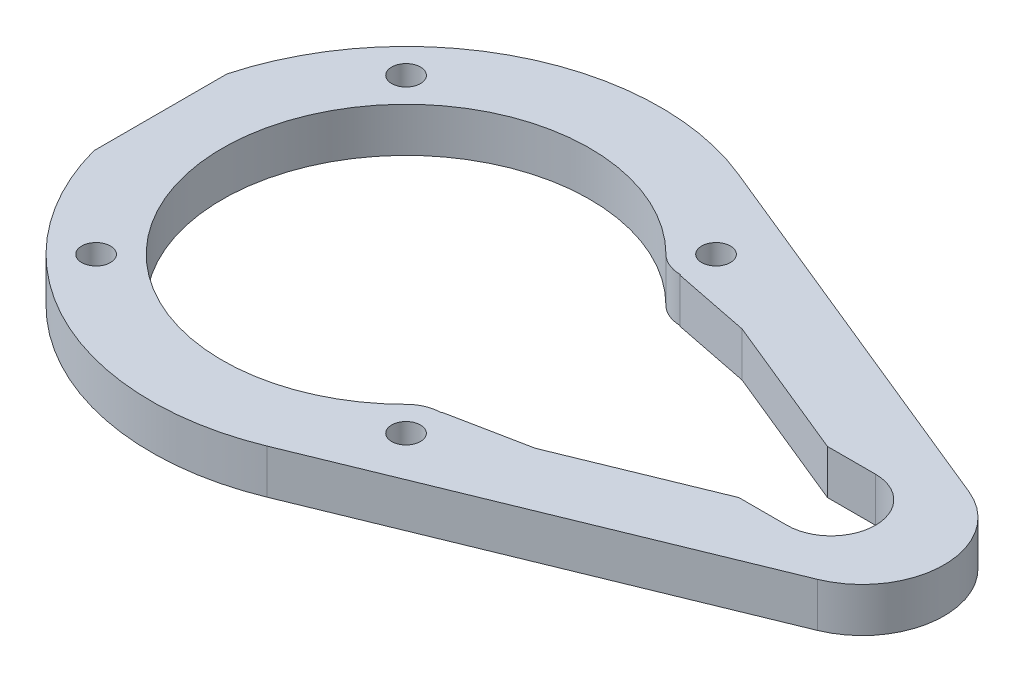
SolidWorks part; units mm, degrees
ref_plane "Front Plane" through (0, 0, 0) normal (0, 0, 1) x (1, 0, 0)
ref_plane "Top Plane" through (0, 0, 0) normal (0, 1, 0) x (1, 0, 0)
ref_plane "Right Plane" through (0, 0, 0) normal (1, 0, 0) x (0, 0, -1)
sketch "Sketch1" plane through (0, 0, 0) normal (0, 1, 0) x (1, 0, 0)
  line L0 (-75.4693, 0) -> (91.4794, 0) construction
  line L1 (35, 35) -> (-35, 35)
  line L2 (35, 35) -> (35, -35)
  line L3 (35, -35) -> (-35, -35)
  line L4 (-35, 35) -> (-35, -35)
  line L5 (35, 35) -> (-35, -35) construction
  line L6 (35, -35) -> (-35, 35) construction
  line L7 (110.0044, 17.1227) -> (21.7695, 53.217)
  line L8 (110.0044, -17.1227) -> (21.7695, -53.217)
  line L9 (86.9809, 9.254) -> (52.5473, 23.3398)
  line L10 (86.9809, -9.254) -> (52.5473, -23.3398)
  line L11 (52.5473, 23.3398) -> (33.4341, 27.1547)
  line L12 (52.5473, -23.3398) -> (33.4341, -27.1547)
  line L13 (-55.5, 15.0236) -> (-55.5, -15.0236)
  line L14 (96, 10) -> (85.1573, 10)
  line L15 (96, -10) -> (85.1573, -10)
  circle A0 centre (-35, 35) radius 3.25
  circle A1 centre (35, 35) radius 3.25
  circle A2 centre (35, -35) radius 3.25
  circle A3 centre (-35, -35) radius 3.25
  circle A4 centre (-35, 35) radius 8
  circle A5 centre (35, 35) radius 8
  circle A6 centre (35, -35) radius 8
  circle A7 centre (-35, -35) radius 8
  circle A8 centre (0, 0) radius 57.4975
  circle A9 centre (0, 0) radius 41.4975
  circle A10 centre (103, 0) radius 18.5
  circle A11 centre (96, 0) radius 10
  point P0 (0, 0)
  dimension "D2" = 6.5
  dimension "D3" = 16
  dimension "D4" = 37
  dimension "D8" = 20
  dimension "D1" = 70
  dimension "D5" = 96
  dimension "D6" = 16
  dimension "D7" = 55.5
  dimension "D9" = 7
extrude "Boss-Extrude1" add sketch "Sketch1" along normal blind 10 contours A9 L1 A5 A8 A4 | L1 A4 L4 A0 | L4 A4 L1 A0 | A9 L1 A4 | A9 L4 A4 A8 A7 | A9 A4 L4 | A9 L4 A7 | A9 A7 L3 | L3 A7 L4 A3 | A9 L3 A7 A8 A6 | L4 A7 L3 A3 | L2 A6 L3 A2 | L3 A6 L2 A2 | A9 L3 A6 | A9 A5 L1 | L1 A5 L2 A1 | L2 A5 L1 A1 | A10 L7 A8 L9 | A10 L10 A8 L8 | A10 | L11 A8 A5 L2 | A6 A8 L12 L2 region at (-31.2062, 0, -31.2062) region at (0, 0, -46.6413) region at (-29.375, 0, -35.2263) region at (-25.7994, 0, -33.5313) region at (-46.2472, 0, 0) region at (-33.5313, 0, -25.7994) region at (25.7994, 0, -33.5313) region at (68.8956, 0, -26.4915) region at (32.0251, 0, -42.182) region at (31.2062, 0, -31.2062) region at (107.2884, 0, 0) region at (45.0485, 0, -28.9885) region at (-33.5313, 0, 25.7994) region at (-42.182, 0, 32.0251) region at (0, 0, 46.6413) region at (-31.2062, 0, 31.2062) region at (-25.7994, 0, 33.5313) region at (68.8956, 0, 26.4915) region at (45.0485, 0, 28.9885) region at (31.2062, 0, 31.2062) region at (25.7994, 0, 33.5313) region at (32.0251, 0, 42.182)
